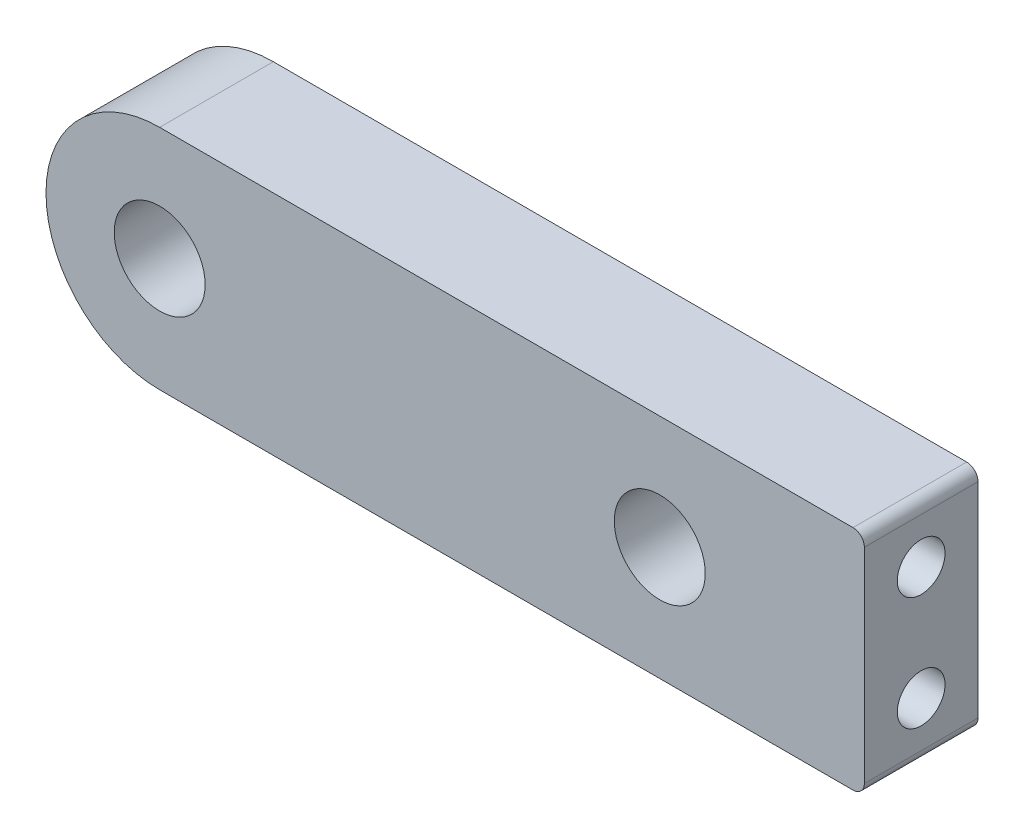
SolidWorks part; units mm, degrees
material "AISI 316 Barre d'acier inoxydable recuit (SS)"
ref_plane "Plan de face" through (0, 0, 0) normal (0, 0, 1) x (1, 0, 0)
ref_plane "Plan de dessus" through (0, 0, 0) normal (0, 1, 0) x (1, 0, 0)
ref_plane "Plan de droite" through (0, 0, 0) normal (1, 0, 0) x (0, 0, -1)
sketch "Esquisse1" plane through (0, 0, 0) normal (0, 0, 1) x (1, 0, 0)
  line L0 (0, 10) -> (72, 10) construction
  line L1 (0, 20) -> (72, 20)
  line L2 (0, 20) -> (0, 0)
  line L3 (0, 0) -> (72, 0)
  line L4 (72, 20) -> (72, 0)
  line L5 (36, 20) -> (36, 0) construction
  circle A0 centre (10, 10) radius 4
  circle A1 centre (54, 10) radius 4
  dimension "D3" = 8
  dimension "D4" = 44
  dimension "D1" = 20
  dimension "D2" = 72
  dimension "D5" = 10
extrude "Boss.-Extru.1" add sketch "Esquisse1" along normal blind 10 contours L2 L4 A1 A0 region at (36.3002, 10, 0)
fillet "Congé1" radius 10 2 edges at (0, 0, 5) (0, 20, 5)
hole_wizard "Trou taraudé M5x0.82" positions "Esquisse5" profile "Esquisse6" tap size "M5x0.8" standard "Ansi Metric"
sketch "Esquisse5" plane through (72, 0, 0) normal (1, 0, 0) x (0, 0, -1)
  line L0 (-5, 20) -> (-5, 0) construction
  line L4 (-10, 10) -> (0, 10) construction
  line L5 (-10, 20) -> (-10, 0) construction
  line L6 (-10, 20) -> (0, 20) construction
  line L7 (-10, 0) -> (0, 0) construction
  line L8 (0, 20) -> (0, 0) construction
  point P0 (-5, 15)
  point P2 (-5, 5)
  dimension "D1" = 10
  dimension "D2" = 10
cosmetic thread "Filetage de perçage2" parameters "D1"=10, "D2"=5
cosmetic thread "Filetage de perçage3" parameters "D1"=10, "D2"=5
sketch "Esquisse6" plane through (72, 15, 5) normal (0, 1, 0) x (0, 0, -1)
  line L0 (0, 0) -> (0, 14)
  line L1 (0, 14) -> (2.1, 14)
  line L2 (2.1, 14) -> (2.1, 0)
  line L5 (2.1, 0) -> (0, 0)
  line L10 (0, 14) -> (-2.1, 14) construction
  line L11 (0, -6.35) -> (0, 107.95) construction
  dimension "Diamètre du trou pour taraudage" = 4.2
  dimension "Profondeur du trou pour taraudage" = 14
  dimension "Angle de pointe" = 180
fillet "Congé2" radius 1 2 edges at (72, 0, 5) (72, 20, 5)
